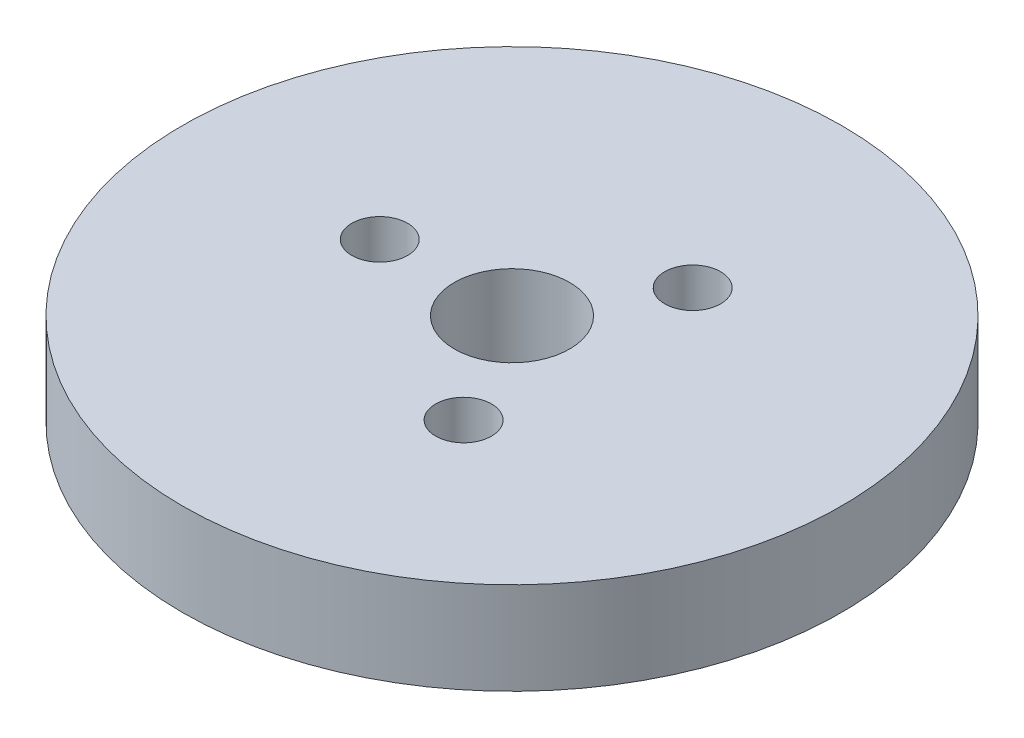
SolidWorks part; units mm, degrees
ref_plane "Front Plane" through (0, 0, 0) normal (0, 0, 1) x (1, 0, 0)
ref_plane "Top Plane" through (0, 0, 0) normal (0, 1, 0) x (1, 0, 0)
ref_plane "Right Plane" through (0, 0, 0) normal (1, 0, 0) x (0, 0, -1)
sketch "Sketch1" plane through (0, 0, 0) normal (0, 1, 0) x (1, 0, 0)
  circle A0 centre (0, 0) radius 100
  dimension "FLANGE_OD" = 200
extrude "Boss-Extrude1" add sketch "Sketch1" along normal blind 28
sketch "Sketch2" plane through (0, 0, 0) normal (0, 1, 0) x (1, 0, 0)
  circle A0 centre (0, 0) radius 17.5
  dimension "BORE_D" = 35
extrude "Cut-Extrude1" cut sketch "Sketch2" along normal through all
sketch "Sketch3" plane through (0, 28, 0) normal (0, 1, 0) x (1, 0, 0)
  circle A0 centre (0, 0) radius 40.1347 construction
  circle A1 centre (-40.1347, 0) radius 8.4747
  dimension "BOLT_D" = 16.9493
  dimension "BOLT_PCD" = 80.2695
extrude "Cut-Extrude2" cut sketch "Sketch3" against normal blind 27.7254
pattern_circular "CirPattern1" count 3 over 360 about axis through (0, 0, 0) along (0, 1, 0) of "Cut-Extrude2"
